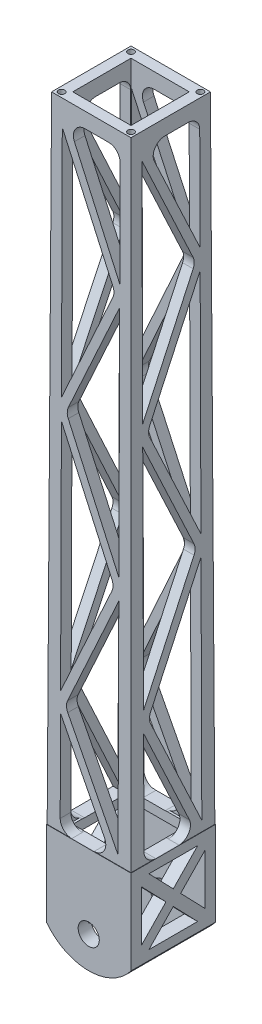
SolidWorks part; units mm, degrees
ref_plane "Front Plane" through (0, 0, 0) normal (0, 0, 1) x (1, 0, 0)
ref_plane "Top Plane" through (0, 0, 0) normal (0, 1, 0) x (1, 0, 0)
ref_plane "Right Plane" through (0, 0, 0) normal (1, 0, 0) x (0, 0, -1)
sketch "Sketch1" plane through (0, 0, 0) normal (0, 1, 0) x (1, 0, 0)
  line L1 (40, 60) -> (-40, 60)
  line L2 (40, 60) -> (40, -20)
  line L3 (40, -20) -> (-40, -20)
  line L4 (-40, 60) -> (-40, -20)
  point P0 (0, 0)
  point P6 (0, 0)
  point P12 (0, -20)
  dimension "D1" = 80
  dimension "D3" = 80
extrude "Boss-Extrude1" add sketch "Sketch1" along normal blind 700 draft 0.2
shell "Shell2" thickness 10 removed face at (0, 700, -20)
sketch "Sketch2" plane through (0, 700, 0) normal (0, 1, 0) x (1, 0, 0)
  line L0 (-27.5565, 47.5565) -> (-41.0313, 61.0313) construction
  line L1 (0, 57.5565) -> (0, 29.7664) construction
  line L2 (37.5565, 57.5565) -> (-37.5565, 57.5565) construction
  line L3 (-37.5565, 20) -> (0, 20) construction
  line L4 (-37.5565, 57.5565) -> (-37.5565, -17.5565) construction
  line L5 (27.5565, 47.5565) -> (41.0313, 61.0313) construction
  line L6 (27.5565, -7.5565) -> (41.0313, -21.0313) construction
  line L7 (-27.5565, -7.5565) -> (-41.0313, -21.0313) construction
  circle A0 centre (-32.808, 52.808) radius 3
  circle A1 centre (32.808, 52.808) radius 3
  circle A2 centre (32.808, -12.808) radius 3
  circle A3 centre (-32.808, -12.808) radius 3
  dimension "D1" = 6
extrude "Cut-Extrude1" cut sketch "Sketch2" against normal blind 10
sketch "Sketch4" plane through (0, 700, 0) normal (0, 1, 0) x (1, 0, 0)
  line L1 (-27.5565, 47.5565) -> (27.5565, 47.5565)
  line L2 (-27.5565, 47.5565) -> (-27.5565, -7.5565)
  line L3 (-27.5565, -7.5565) -> (27.5565, -7.5565)
  line L4 (27.5565, 47.5565) -> (27.5565, -7.5565)
extrude "Cut-Extrude2" cut sketch "Sketch4" against normal through all both and the other way through all
sketch "Sketch5" plane through (0, 0, 0) normal (0, -1, 0) x (1, 0, 0)
  line L1 (-40, 20) -> (40, 20)
  line L2 (-40, 20) -> (-40, -60)
  line L3 (-40, -60) -> (40, -60)
  line L4 (40, 20) -> (40, -60)
  line L5 (-27.5565, 7.5565) -> (27.5565, 7.5565)
  line L6 (-27.5565, 7.5565) -> (-27.5565, -47.5565)
  line L7 (-27.5565, -47.5565) -> (27.5565, -47.5565)
  line L8 (27.5565, 7.5565) -> (27.5565, -47.5565)
sketch "Sketch8" plane through (0, 0, 0) normal (0, -1, 0) x (1, 0, 0)
  line L1 (-40, 20) -> (40, 20)
  line L2 (-40, 20) -> (-40, -60)
  line L3 (-40, -60) -> (40, -60)
  line L4 (40, 20) -> (40, -60)
  line L5 (-27.5565, 7.5565) -> (27.5565, 7.5565)
  line L6 (-27.5565, 7.5565) -> (-27.5565, -47.5565)
  line L7 (-27.5565, -47.5565) -> (27.5565, -47.5565)
  line L8 (27.5565, 7.5565) -> (27.5565, -47.5565)
extrude "Boss-Extrude3" add sketch "Sketch8" against normal blind 100
sketch "Sketch9" plane through (0, 0, 20) normal (0, 0, 1) x (1, 0, 0)
  line L0 (-40, 100) -> (-40, 0) construction
  circle A0 centre (0, 30) radius 10
  dimension "D1" = 20
  dimension "D2" = 40
  dimension "D3" = 30
extrude "Cut-Extrude4" cut sketch "Sketch9" against normal through all both and the other way through all contours A0
sketch "Sketch10" plane through (0, 0, 20) normal (0, 0, 1) x (1, 0, 0)
  line L0 (40, 0) -> (-40, 0)
  line L1 (-40, 0) -> (-40, 19.8762)
  line L2 (-40, 100) -> (-40, 0) construction
  line L3 (0, 0) -> (0, 26.6715) construction
  line L4 (40, 0) -> (40, 19.8762)
  circle A0 centre (0, 50.1873) radius 50.1873
  line M3 (-40, 0) -> (40, 0)
  line M4 (40, 0) -> (40, 100)
  line M6 (-40, 100) -> (-40, 0)
extrude "Cut-Extrude5" cut sketch "Sketch10" against normal through all both and the other way through all contours A0 M6 M3 | A0 L0 M4 region at (30.439, 5.6865, 20) region at (-30.439, 5.6865, 20)
sketch "Sketch11" plane through (39.9995, 0.1396, 0) normal (1, 0.0035, 0) x (0, 0, -1)
  line L0 (20, 99.861) -> (20, 699.8646) construction
  line L1 (59.6509, 99.861) -> (-19.6509, 99.861) construction
  line L2 (-17.5565, 699.8646) -> (57.5565, 699.8646) construction
sketch "Sketch13" plane through (39.9995, 0.1396, 0) normal (1, 0.0035, 0) x (0, 0, -1)
  line L0 (47.3608, 99.861) -> (47.3608, 685.3242)
  line L1 (47.3608, 99.861) -> (-7.3608, 99.861)
  line L3 (47.3608, 685.3242) -> (-7.3608, 685.3242)
  line L4 (-7.3608, 99.861) -> (-7.3608, 685.3242)
sketch "Sketch14" plane through (0, 0.2094, -59.9993) normal (0, 0.0035, -1) x (-1, 0, 0)
  line L0 (0, 385.6446) -> (0, -52.7487) construction
  circle A0 centre (0, 167.3784) radius 11
  circle A1 centre (0, 306.6307) radius 11
  circle A2 centre (0, 439.3151) radius 11
  circle A3 centre (0, 573.2293) radius 11
  dimension "D1" = 22
sketch "Sketch16" plane through (40, 0, 0) normal (1, 0, 0) x (0, 0, -1)
  line L0 (20, 100) -> (20, 19.8762) construction
  line L1 (60, 19.8762) -> (-20, 19.8762) construction
  line L2 (-20, 59.9381) -> (60, 59.9381) construction
  line L3 (-20, 100) -> (-20, 19.8762) construction
  line L4 (60, 100) -> (60, 19.8762) construction
  line L6 (50, 28.8762) -> (-10, 28.8762)
  line L7 (50, 28.8762) -> (50, 91)
  line L8 (50, 91) -> (-10, 91)
  line L9 (-10, 28.8762) -> (-10, 91)
  line L10 (50, 28.8762) -> (-10, 91) construction
  line L11 (50, 91) -> (-10, 28.8762) construction
  point P11 (20, 59.9381)
extrude "Cut-Extrude7" cut sketch "Sketch16" against normal through all both and the other way through all
sketch "Sketch17" plane through (40, 0, 0) normal (1, 0, 0) x (0, 0, -1)
  line L0 (-10, 91) -> (50, 28.8762) construction
  line L1 (50, 28.8762) -> (50, 91) construction
  line L2 (50, 91) -> (-10, 91) construction
  line L3 (-10, 91) -> (-10, 28.8762) construction
  line L4 (-10, 28.8762) -> (50, 91) construction
  line L5 (20, 91) -> (20, 28.8762) construction
  line L6 (-10, 28.8762) -> (50, 28.8762) construction
  line L7 (-10, 59.9381) -> (50, 59.9381) construction
  line L8 (-3.0487, 91) -> (20, 67.1354)
  line L9 (43.0487, 91) -> (20, 67.1354)
  line L10 (43.0487, 28.8762) -> (20, 52.7408)
  line L11 (-3.0487, 28.8762) -> (20, 52.7408)
  line L12 (-10, 83.8027) -> (13.0487, 59.9381)
  line L13 (-10, 36.0735) -> (13.0487, 59.9381)
  line L14 (50, 36.0735) -> (26.9513, 59.9381)
  line L15 (50, 83.8027) -> (26.9513, 59.9381)
  line L16 (-3.0487, 91) -> (-10, 91)
  line L17 (-10, 91) -> (-10, 83.8027)
  line L18 (43.0487, 91) -> (50, 91)
  line L19 (50, 91) -> (50, 83.8027)
  line L20 (50, 36.0735) -> (50, 28.8762)
  line L21 (50, 28.8762) -> (43.0487, 28.8762)
  line L22 (-3.0487, 28.8762) -> (-10, 28.8762)
  line L23 (-10, 28.8762) -> (-10, 36.0735)
  dimension "D1" = 5
  dimension "D2" = 5
extrude "Boss-Extrude5" add sketch "Sketch17" against normal blind 12
sketch "Sketch20" plane through (0, 0.0698, 19.9998) normal (0, 0.0035, 1) x (1, 0, 0)
  line L0 (0, 699.9345) -> (0, 685.5945) construction
  line L1 (-37.5565, 699.9345) -> (37.5565, 699.9345) construction
  line L2 (-27.36, 205.5945) -> (27.36, 99.9296) construction
  line L3 (27.36, 685.5945) -> (27.36, 99.9296)
  line L4 (27.36, 685.5945) -> (-27.36, 685.5945)
  line L5 (-27.36, 685.5945) -> (27.36, 565.5945) construction
  line L6 (27.36, 99.9296) -> (-27.36, 99.9296)
  line L7 (-27.36, 685.5945) -> (-27.36, 99.9296)
  line L8 (27.36, 565.5945) -> (-27.36, 565.5945) construction
  line L9 (-27.36, 445.5945) -> (27.36, 565.5945) construction
  line L10 (-27.36, 445.5945) -> (27.36, 445.5945) construction
  line L11 (-27.36, 445.5945) -> (27.36, 325.5945) construction
  line L12 (27.36, 325.5945) -> (-27.36, 325.5945) construction
  line L13 (-27.36, 205.5945) -> (27.36, 325.5945) construction
  line L14 (-27.36, 205.5945) -> (27.36, 205.5945) construction
  line L15 (27.36, 99.9296) -> (28.0264, 71.5055) construction
  line L16 (-22.9638, 685.5945) -> (27.36, 575.2353)
  line L17 (-27.36, 675.9536) -> (22.9638, 565.5945)
  line L18 (-27.36, 455.2353) -> (22.9638, 565.5945)
  line L19 (-22.9638, 445.5945) -> (27.36, 555.9536)
  line L20 (-22.9638, 445.5945) -> (27.36, 335.2353)
  line L21 (-27.36, 435.9536) -> (22.9638, 325.5945)
  line L22 (-27.36, 215.2353) -> (22.9638, 325.5945)
  line L23 (-22.9638, 205.5945) -> (27.36, 315.9536)
  line L24 (-22.9638, 205.5945) -> (27.36, 108.4188)
  line L25 (-27.36, 196.8961) -> (22.8555, 99.9296)
  line L27 (40, 99.9296) -> (-40, 99.9296) construction
  point P23 (0, 565.5945)
  line M20 (-39.6509, 99.9308) -> (39.6509, 99.9308)
  dimension "D1" = 14.34
  dimension "D2" = 120
  dimension "D3" = 27.36
  dimension "D4" = 27.36
  dimension "D5" = 4
  dimension "D6" = 4
  dimension "D7" = 4
extrude "Cut-Extrude8" cut sketch "Sketch20" against normal blind 111 contours L4 L16 L3 | L7 L18 L17 | L19 L20 L3 | L7 L22 L21 | L23 L24 L3 | L25 L7 M20 region at (10.5854, 648.8739, 17.735) region at (10.5854, 445.6615, 18.4443) region at (-10.5854, 565.6608, 18.0255) region at (10.5854, 210.0575, 19.2668) region at (-10.5854, 325.6623, 18.8632) region at (-10.6217, 132.3216, 19.5381)
fillet "Fillet1" radius 11 16 edges at (-27.36, 99.9789, 13.6037) (22.8548, 99.9789, 13.6037) (22.9638, 325.4084, -53.8641) (-22.9638, 445.4106, -53.4452) (-22.9638, 205.6456, 14.2821) (-22.9638, 205.4062, -54.283) (22.9638, 325.6448, 13.8633) (-22.9638, 445.6441, 13.4444) (22.9638, 565.4128, -53.0263) (22.9638, 565.6434, 13.0255) (-22.9638, 685.6426, 12.6066) (-22.9638, 685.415, -52.6074) (27.36, 685.415, -52.6074) (27.36, 685.6426, 12.6066) (-27.36, 99.7437, -53.7782) (22.8548, 99.7437, -53.7782)
sketch "Sketch22" plane through (39.9995, 0.1396, 0) normal (1, 0.0035, 0) x (0, 0, -1)
  line L0 (-7.3608, 685.3242) -> (47.3608, 568.2322) construction
  line L1 (-7.3608, 685.3242) -> (47.3608, 685.3242)
  line L2 (-7.3608, 685.3242) -> (-7.3608, 207.5085)
  line L3 (-7.3608, 207.5085) -> (-7.3608, 99.861)
  line L4 (47.3608, 685.3242) -> (47.3608, 99.861)
  line L5 (47.3608, 568.2322) -> (-7.3608, 568.2322) construction
  line L6 (-7.3608, 451.1402) -> (47.3608, 568.2322) construction
  line L7 (-7.3608, 451.1402) -> (47.3608, 451.1402) construction
  line L8 (-7.3608, 451.1402) -> (47.3608, 334.0482) construction
  line L9 (47.3608, 334.0482) -> (-7.3608, 334.0482) construction
  line L10 (-7.3608, 216.9562) -> (47.3608, 334.0482) construction
  line L11 (-7.3608, 216.9562) -> (47.3608, 216.9562) construction
  line L12 (-7.3608, 216.9562) -> (47.3608, 99.8642) construction
  line L13 (-2.9456, 685.3242) -> (47.3608, 577.6798)
  line L14 (-7.3608, 675.8765) -> (42.9456, 568.2322)
  line L16 (-7.3608, 460.5878) -> (42.9456, 568.2322)
  line L17 (-2.9456, 451.1402) -> (47.3608, 558.7845)
  line L18 (-2.9456, 451.1402) -> (47.3608, 343.4958)
  line L19 (-7.3608, 441.6925) -> (42.9456, 334.0482)
  line L20 (-7.3608, 226.4038) -> (42.9456, 334.0482)
  line L21 (-2.9456, 216.9562) -> (47.3608, 324.6005)
  line L22 (-2.9456, 216.9562) -> (47.3608, 109.3118)
  line L23 (-7.3608, 207.5085) -> (42.9456, 99.8642)
  line L24 (-7.3608, 99.861) -> (42.9456, 99.8642)
  dimension "D1" = 117.092
  dimension "D2" = 4
  dimension "D3" = 4
extrude "Cut-Extrude11" cut sketch "Sketch22" against normal through all both and the other way through all contours L21 L22 L4 | L2 L20 L19 | L17 L18 L4 | L2 L16 L14 | L1 L13 L4 | L3 L24 L23 region at (39.2422, 217.0945, -30.592) region at (38.4247, 451.277, -30.592) region at (37.7325, 649.5784, -30.592) region at (38.8335, 334.1857, -9.408) region at (38.016, 568.3683, -9.408)
fillet "Fillet2" radius 11 14 edges at (-32.6081, 685.2145, 2.9456) (32.6073, 685.4422, 2.9456) (-32.6081, 685.2145, -47.3608) (32.6073, 685.4422, -47.3608) (-33.0168, 568.1204, -42.9456) (33.016, 568.3509, -42.9456) (33.4248, 451.2596, 2.9456) (-33.8343, 333.9321, -42.9456) (33.8335, 334.1683, -42.9456) (-34.2431, 216.8379, 2.9456) (34.2422, 217.077, 2.9456) (33.6037, 99.9821, -42.9456) (-33.7782, 99.7437, 7.3608) (33.6037, 99.9789, 7.3608)
extrude "Boss-Extrude6" add sketch "Sketch17<3>" against normal blind 12 from offset 68 offset against normal yes
sketch "Sketch17<3>" plane through (40, 0, 0) normal (1, 0, 0) x (0, 0, -1) same geometry as "Sketch17"
